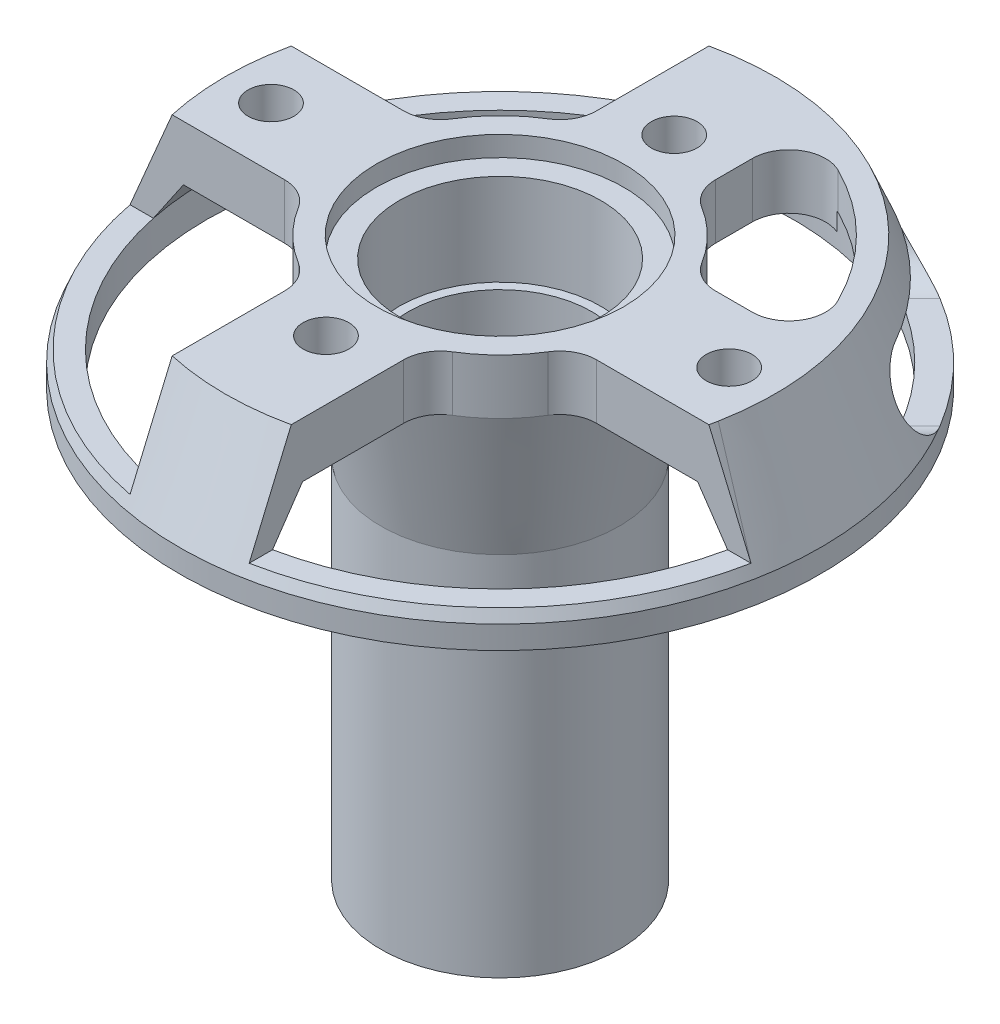
SolidWorks part; units mm, degrees
material "6061-T6 (SS)"
ref_plane "Front Plane" through (0, 0, 0) normal (0, 0, 1) x (1, 0, 0)
ref_plane "Top Plane" through (0, 0, 0) normal (0, 1, 0) x (1, 0, 0)
ref_plane "Right Plane" through (0, 0, 0) normal (1, 0, 0) x (0, 0, -1)
sketch "Sketch1" plane through (0, 0, 0) normal (0, 0, 1) x (1, 0, 0)
  line L0 (0, 15.0763) -> (0, -19.3628) construction
  line L1 (0, 0) -> (17.5, 0)
  line L2 (17.5, 0) -> (17.5, 1.25)
  line L3 (17.5, 1.25) -> (15, 7.25)
  line L4 (15, 7.25) -> (0, 7.25)
  line L5 (0, 7.25) -> (0, 0)
  dimension "D1" = 35
  dimension "D2" = 1.25
  dimension "D3" = 7.25
  dimension "D4" = 30
revolve "Bottom Base" add sketch "Sketch1" angle 360 about L0
sketch "Sketch2" plane through (0, 0, 0) normal (0, 0, 1) x (1, 0, 0)
  line L0 (16, 0) -> (16, 1.85)
  line L1 (-17.5, 0) -> (17.5, 0) construction
  line L2 (16, 1.85) -> (14.4, 4.25)
  line L3 (14.4, 4.25) -> (0, 4.25)
  line L4 (0, 4.25) -> (0, 0)
  line L5 (0, 0) -> (16, 0)
  line L6 (17.5, 1.25) -> (17.5, 0)
  line L7 (-17.5, 0) -> (-17.5, 1.25)
  line L8 (15, 7.25) -> (-15, 7.25) construction
  line L9 (17.5, 1.25) -> (17.5, 0) construction
  line L10 (-17.5, 1.25) -> (-15, 7.25)
  line L11 (15, 7.25) -> (17.5, 1.25)
  line L12 (15, 7.25) -> (17.5, 1.25) construction
  dimension "D1" = 1.5
  dimension "D2" = 3
  dimension "D3" = 1.85
  dimension "D4" = 0.6
revolve "Cut-Revolve1" cut sketch "Sketch2" angle 360 about L4
sketch "Sketch3" plane through (0, 7.25, 0) normal (0, 1, 0) x (1, 0, 0)
  circle A0 centre (0, 0) radius 6.75
  dimension "D1" = 13.5
extrude "Cut-Extrude1" cut sketch "Sketch3" against normal blind 1.1
sketch "Sketch4" plane through (0, 0, 0) normal (0, 0, 1) x (1, 0, 0)
  line L0 (-8, 4.25) -> (-6.5, -3.25)
  line L1 (-14.4, 4.25) -> (14.4, 4.25) construction
  line L2 (-6.5, -3.25) -> (-6.5, -23.25)
  line L3 (-6.5, -23.25) -> (0, -23.25)
  line L4 (0, -23.25) -> (0, 4.25)
  line L5 (0, 4.25) -> (-8, 4.25)
  line L6 (15, 7.25) -> (-15, 7.25) construction
  dimension "D1" = 8
  dimension "D2" = 30.5
  dimension "D3" = 6.5
  dimension "D4" = 20
revolve "Revolve2" add sketch "Sketch4" angle 360 about L4
sketch "Sketch5" plane through (0, 6.15, 0) normal (0, 1, 0) x (1, 0, 0)
  circle A0 centre (0, 0) radius 5.5
  dimension "D1" = 11
extrude "Bore" cut sketch "Sketch5" against normal through all
sketch "Sketch6" plane through (0, 7.25, 0) normal (0, 1, 0) x (1, 0, 0)
  line L0 (0, 0) -> (-17.5, 0) construction
  line L1 (0, 0) -> (0, 17.5) construction
  line L2 (-17.1956, 3.25) -> (-7.3101, 3.25)
  line L3 (-3.25, 17.1956) -> (-3.25, 7.3101)
  circle A0 centre (0, 0) radius 17.5 construction
  circle A1 centre (0, 0) radius 8 construction
  circle A2 centre (0, 0) radius 8 construction
  arc A3 (-17.1956, 3.25) -> (-3.25, 17.1956) centre (0, 0) cw
  arc A4 (-7.3101, 3.25) -> (-3.25, 7.3101) centre (0, 0) cw
  dimension "D1" = 6.5
  dimension "D2" = 6.5
extrude "Weight Relief" cut sketch "Sketch6" against normal offset from surface (5.4 mm away) 1.85 up to face at (-16, 0, 0)
fillet "Weight Relief Fillet" radius 2 2 edges at (-3.25, 5.75, -7.3101) (-7.3101, 5.75, -3.25)
pattern_circular "CirPattern1" count 3 every 90 about axis through (0, -23.25, 0) along (0, 1, 0) of "Weight Relief", "Weight Relief Fillet"
sketch "Sketch7" plane through (0, 7.25, 0) normal (0, 1, 0) x (1, 0, 0)
  line L0 (3.25, 13.3604) -> (3.25, 7.3101)
  line L1 (7.3101, 3.25) -> (13.3604, 3.25)
  line L2 (-3.25, 8.511) -> (-3.25, 14.6437) construction
  line L3 (14.6437, -3.25) -> (8.511, -3.25) construction
  arc A0 (3.25, 7.3101) -> (7.3101, 3.25) centre (0, 0) cw
  arc A1 (13.3604, 3.25) -> (3.25, 13.3604) centre (0, 0) ccw
  circle A2 centre (0, 0) radius 6.75 construction
  arc A3 (-4.2, 6.8088) -> (-6.8088, 4.2) centre (0, 0) ccw construction
  arc A4 (14.6437, -3.25) -> (-3.25, 14.6437) centre (0, 0) ccw construction
  dimension "D1" = 6.5
  dimension "D2" = 6.5
  dimension "D3" = 1.25
extrude "Cut-Extrude4" cut sketch "Sketch7" against normal through all
fillet "Fillet2" radius 2 4 edges at (3.25, 5.75, -7.3101) (7.3101, 5.75, -3.25) (13.3604, 5.75, -3.25) (3.25, 5.75, -13.3604)
ref_plane "Plane1" through (12.3744, 0, -12.3744) normal (0.7071, 0, -0.7071) x (0, 1, 0)
sketch "Sketch8" plane through (12.3744, 0, -12.3744) normal (0.7071, 0, -0.7071) x (0, 1, 0)
  line L0 (3.25, -4.25) -> (3.25, 4.25) construction
  line L1 (1.25, -4.25) -> (1.25, 4.25)
  line L2 (5.25, -4.25) -> (5.25, 4.25)
  line L3 (1.25, 17.5) -> (1.25, -17.5) construction
  line L4 (3.25, 0) -> (0, 0) construction
  arc A0 (1.25, -4.25) -> (5.25, -4.25) centre (3.25, -4.25) ccw
  arc A1 (5.25, 4.25) -> (1.25, 4.25) centre (3.25, 4.25) ccw
  point P2 (3.25, 0)
  point P12 (3.25, 6.25)
  point P13 (3.25, -6.25)
  dimension "D1" = 4
  dimension "D2" = 12.5
extrude "Cut-Extrude5" cut sketch "Sketch8" against normal blind 4.5
sketch "Sketch10" plane through (0, 7.25, 0) normal (0, 1, 0) x (1, 0, 0)
  line L0 (-12.5, 0) -> (12.5, 0) construction
  line L1 (0, -9.5) -> (0, 9.5) construction
  point P5 (0, 9.5)
  point P7 (12.5, 0)
  point P8 (0, -9.5)
  point P9 (-12.5, 0)
  dimension "D1" = 25
  dimension "D2" = 19
hole_wizard "M3x0.5 Tapped Hole1" positions "Sketch11" profile "Sketch13" tap size "M3x0.5" standard "ANSI Metric" end condition through all
sketch "Sketch11" plane through (0, 7.25, 0) normal (0, 1, 0) x (1, 0, 0)
  point P0 (0, 9.5)
  point P3 (12.5, 0)
  point P6 (0, -9.5)
  point P9 (-12.5, 0)
sketch "Sketch13" plane through (0, 7.25, -9.5) normal (1, 0, 0) x (0, 0, 1)
  line L0 (0, 0) -> (0, 30.5)
  line L1 (0, 30.5) -> (1.25, 30.5)
  line L2 (1.25, 30.5) -> (1.25, 0)
  line L5 (1.25, 0) -> (0, 0)
  line L11 (0, -6.35) -> (0, 107.95) construction
  dimension "Thru Tap Drill Dia." = 2.5
  dimension "Thru Tap Drill Depth" = 30.5
cosmetic thread "Hole Thread1" parameters "D2"=3
cosmetic thread "Hole Thread2" parameters "D2"=3
cosmetic thread "Hole Thread3" parameters "D2"=3
cosmetic thread "Hole Thread4" parameters "D2"=3
sketch "Sketch14" plane through (0, 6.15, 0) normal (0, 1, 0) x (1, 0, 0)
  circle A0 centre (0, 0) radius 3.75
  circle A1 centre (0, 0) radius 5.5 construction
  circle A2 centre (0, 0) radius 5.5
  dimension "D1" = 7.5
extrude "Boss-Extrude1" add sketch "Sketch14" against normal offset from surface (19.4 mm away) 5 from offset 5 up to face at (-5.5, -23.25, 0) offset against normal yes
sketch "Sketch9" plane through (0, 6.15, 0) normal (0, 1, 0) x (1, 0, 0)
  circle A0 centre (0, 0) radius 5
  dimension "D1" = 10
extrude "10mm Bore" cut sketch "Sketch9" against normal through all
equation "\"D2@Sketch6\"=\"D1@Sketch6\""
equation "\"D2@Sketch7\"=\"D1@Sketch7\""
